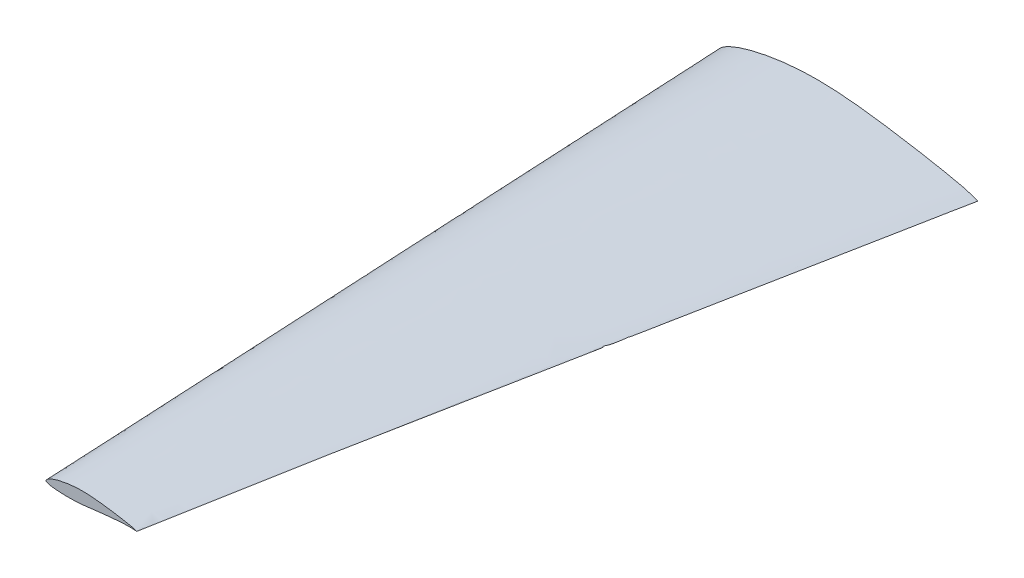
SolidWorks part; units mm, degrees
ref_plane "Front Plane" through (0, 0, 0) normal (0, 0, 1) x (1, 0, 0)
ref_plane "Top Plane" through (0, 0, 0) normal (0, 1, 0) x (1, 0, 0)
ref_plane "Right Plane" through (0, 0, 0) normal (1, 0, 0) x (0, 0, -1)
curve "Curve1"
  spline degree 3 poles (0.9921, 0.0008, 0) (1.0019, -0.0008, 0) (0.9929, 0.0016, 0) (0.9861, 0.0043, 0) (0.9706, 0.0096, 0) (0.9519, 0.0152, 0) (0.9278, 0.021, 0) (0.8992, 0.0273, 0) (0.8662, 0.0341, 0) (0.8293, 0.0413, 0) (0.789, 0.0488, 0) (0.746, 0.0564, 0) (0.7007, 0.0641, 0) (0.6538, 0.0714, 0) (0.6058, 0.0784, 0) (0.5573, 0.0846, 0) (0.5088, 0.0898, 0) (0.4609, 0.0938, 0) (0.4138, 0.0961, 0) (0.3679, 0.0966, 0) (0.3232, 0.0952, 0) (0.2801, 0.092, 0) (0.2388, 0.0874, 0) (0.1997, 0.0815, 0) (0.1631, 0.0746, 0) (0.1296, 0.0669, 0) (0.0993, 0.0585, 0) (0.0726, 0.0496, 0) (0.0499, 0.0404, 0) (0.0312, 0.031, 0) (0.0168, 0.0217, 0) (0.0085, 0.0145, 0) (0.0039, 0.009, 0) (0.0018, 0.0058, 0) (0.0004, 0.0024, 0) (0, 0.0003, 0) (0, -0.0012, 0) (0.0006, -0.0026, 0) (0.002, -0.0043, 0) (0.0049, -0.007, 0) (0.0107, -0.0108, 0) (0.0215, -0.0156, 0) (0.0378, -0.0206, 0) (0.0598, -0.0253, 0) (0.0864, -0.0294, 0) (0.1174, -0.033, 0) (0.1523, -0.036, 0) (0.1908, -0.0383, 0) (0.2323, -0.0397, 0) (0.2764, -0.0402, 0) (0.3228, -0.0395, 0) (0.3711, -0.0373, 0) (0.4212, -0.0335, 0) (0.4729, -0.0284, 0) (0.526, -0.0227, 0) (0.5798, -0.0169, 0) (0.6336, -0.0114, 0) (0.6866, -0.0064, 0) (0.7378, -0.0023, 0) (0.7866, 0.0009, 0) (0.832, 0.0031, 0) (0.8733, 0.0042, 0) (0.9096, 0.0045, 0) (0.9406, 0.0038, 0) (0.9645, 0.0029, 0) (0.984, 0.0013, 0) (0.9921, 0.0008, 0) (1.0019, -0.0008, 0) (0.9929, 0.0016, 0) knots -0.016161 -0.007282 -0.001839 0 0.00178 0.006777 0.014308 0.024046 0.036116 0.050547 0.06713 0.085624 0.105767 0.127282 0.149864 0.17323 0.197069 0.221103 0.245052 0.268663 0.291773 0.314299 0.336178 0.357377 0.377792 0.397225 0.415489 0.432417 0.447849 0.461651 0.473687 0.483898 0.492263 0.498797 0.499955 0.502811 0.504371 0.50536 0.505925 0.506503 0.507535 0.509205 0.512345 0.517665 0.526422 0.537425 0.550643 0.565966 0.583206 0.602155 0.622587 0.644255 0.666998 0.690703 0.715307 0.740824 0.767084 0.793717 0.820331 0.846519 0.871863 0.895937 0.918335 0.938667 0.956573 0.971715 0.983839 0.992718 0.998161 1 1.00178 1.006777 1.014308 periodic
sketch "Sketch1" plane through (0, 0, 0) normal (0, 0, 1) x (1, 0, 0)
  line L0 (1122.2059, -30.8288) -> (-1162.7941, -35.0845) construction
  spline S1 degree 3 poles (1104.1363, -28.0222) (1126.6295, -31.7875) (1105.8826, -26.3024) (1090.4575, -20.1288) (1054.9513, -7.9956) (1012.296, 4.6638) (957.0478, 17.8508) (891.7164, 32.0367) (816.2153, 47.3864) (731.9108, 63.6705) (639.9041, 80.612) (541.5101, 97.9168) (438.0076, 115.0958) (330.7593, 131.7488) (221.0675, 147.3336) (110.2357, 161.251) (-0.493, 172.9975) (-110.0556, 181.8587) (-217.6516, 186.9061) (-322.6724, 187.859) (-424.6755, 184.4831) (-523.1626, 176.9995) (-617.5035, 166.1709) (-706.8843, 152.6667) (-790.3524, 136.737) (-867.0563, 118.889) (-936.2082, 99.5088) (-997.0691, 79.0242) (-1049.0447, 57.9028) (-1091.6336, 36.4479) (-1124.4686, 15.1943) (-1143.3869, -1.4067) (-1153.8659, -14.0298) (-1158.6984, -21.3016) (-1161.9612, -29.0988) (-1162.8988, -33.8887) (-1162.7223, -37.2464) (-1161.3764, -40.4052) (-1158.2301, -44.4654) (-1151.5185, -50.6376) (-1138.2079, -59.2164) (-1113.635, -70.0567) (-1076.2399, -81.3981) (-1026.0446, -92.1031) (-965.2298, -101.4019) (-894.4776, -109.4657) (-814.6314, -116.0953) (-726.7099, -121.1028) (-631.8133, -124.2931) (-530.9633, -125.2112) (-425.0342, -123.2363) (-314.6436, -117.9744) (-200.1569, -109.1265) (-81.9663, -97.1903) (39.2548, -83.9633) (162.1641, -70.4688) (285.0306, -57.6215) (406.0083, -46.0046) (523.1884, -36.2734) (634.6311, -28.7415) (738.3789, -23.5277) (832.7109, -20.7776) (915.5317, -20.0924) (986.36, -21.3847) (1040.9806, -23.338) (1085.6437, -26.9173) (1104.1363, -28.0222) (1126.6295, -31.7875) (1105.8826, -26.3024) knots -0.016161 -0.007282 -0.001839 0 0.00178 0.006777 0.014308 0.024046 0.036116 0.050547 0.06713 0.085624 0.105767 0.127282 0.149864 0.17323 0.197069 0.221103 0.245052 0.268663 0.291773 0.314299 0.336178 0.357377 0.377792 0.397225 0.415489 0.432417 0.447849 0.461651 0.473687 0.483898 0.492263 0.498797 0.499955 0.502811 0.504371 0.50536 0.505925 0.506503 0.507535 0.509205 0.512345 0.517665 0.526422 0.537425 0.550643 0.565966 0.583206 0.602155 0.622587 0.644255 0.666998 0.690703 0.715307 0.740824 0.767084 0.793717 0.820331 0.846519 0.871863 0.895937 0.918335 0.938667 0.956573 0.971715 0.983839 0.992718 0.998161 1 1.00178 1.006777 1.014308 only from (1122.2059, -30.8288) to (1122.2059, -30.8288)
  dimension "D1" = 2285
ref_plane "Plane1" through (0, 0, 6200) normal (0, 0, 1) x (1, 0, 0)
ref_plane "Plane3" through (0, -35.0845, 0) normal (0, 1, 0) x (1, 0, 0)
sketch "Sketch4" plane through (0, -35.0845, 0) normal (0, 1, 0) x (1, 0, 0)
  line L1 (1122.2059, 0) -> (-1162.7941, 0) construction
  line L2 (-172.1886, -6200) -> (172.1886, -6200) construction
  line L4 (-1162.7941, 0) -> (-862.7941, -6200)
sketch "Sketch5" plane through (0, 0, 6200) normal (0, 0, 1) x (1, 0, 0)
  line L0 (-62.749, -35.2354) -> (-862.7688, -35.3009) construction
  spline S1 degree 3 poles (-69.0897, -34.3504) (-61.22, -35.5469) (-68.4893, -33.741) (-73.9048, -31.6671) (-86.3598, -27.6181) (-101.3126, -23.4229) (-120.663, -19.1093) (-143.5377, -14.4998) (-169.9677, -9.5373) (-199.4749, -4.2947) (-231.6736, 1.1372) (-266.1033, 6.6624) (-302.3153, 12.1171) (-339.8318, 17.3686) (-378.1955, 22.2345) (-416.9483, 26.5125) (-455.6538, 30.0335) (-493.9373, 32.5536) (-531.5145, 33.7529) (-568.1715, 33.5367) (-603.7528, 31.8256) (-638.0855, 28.6992) (-670.9538, 24.4271) (-702.0769, 19.2472) (-731.124, 13.2516) (-757.8002, 6.6219) (-781.8329, -0.5031) (-802.9662, -7.9701) (-820.9952, -15.6131) (-835.7466, -23.3233) (-847.0949, -30.9123) (-853.6106, -36.8049) (-857.2018, -41.2651) (-858.8503, -43.8282) (-859.9483, -46.5664) (-860.2505, -48.243) (-860.1714, -49.4139) (-859.6851, -50.5093) (-858.5659, -51.9099) (-856.1913, -54.0289) (-851.5011, -56.9533) (-842.8685, -60.6082) (-829.7584, -64.3709) (-812.1844, -67.8447) (-790.9116, -70.7722) (-766.1771, -73.2167) (-738.2762, -75.1133) (-707.5656, -76.4015) (-674.4302, -77.0191) (-639.2289, -76.8125) (-602.2702, -75.5698) (-563.7715, -73.1566) (-523.8621, -69.4706) (-482.6761, -64.6873) (-440.4393, -59.4377) (-397.6147, -54.086) (-354.8016, -48.9603) (-312.6413, -44.2739) (-271.7964, -40.2655) (-232.9425, -37.0546) (-196.7619, -34.6929) (-163.8546, -33.2402) (-134.9538, -32.5684) (-110.2281, -32.6493) (-91.1554, -33.0456) (-75.5494, -34.0614) (-69.0897, -34.3504) (-61.22, -35.5469) (-68.4893, -33.741) knots -0.016161 -0.007282 -0.001839 0 0.00178 0.006777 0.014308 0.024046 0.036116 0.050547 0.06713 0.085624 0.105767 0.127282 0.149864 0.17323 0.197069 0.221103 0.245052 0.268663 0.291773 0.314299 0.336178 0.357377 0.377792 0.397225 0.415489 0.432417 0.447849 0.461651 0.473687 0.483898 0.492263 0.498797 0.499955 0.502811 0.504371 0.50536 0.505925 0.506503 0.507535 0.509205 0.512345 0.517665 0.526422 0.537425 0.550643 0.565966 0.583206 0.602155 0.622587 0.644255 0.666998 0.690703 0.715307 0.740824 0.767084 0.793717 0.820331 0.846519 0.871863 0.895937 0.918335 0.938667 0.956573 0.971715 0.983839 0.992718 0.998161 1 1.00178 1.006777 1.014308 only from (-62.7688, -35.2354) to (-62.7688, -35.2354)
  point P3 (-862.7688, -35.3009)
  point P4 (0, 0)
  dimension "D1" = 800
sketch "Sketch6" plane through (0, 0, 6200) normal (0, 0, 1) x (1, 0, 0)
  line L0 (-862.7688, -35.3009) -> (-860.1517, -49.246)
  spline S0 degree 3 poles (-69.0897, -34.3504) (-61.22, -35.5469) (-68.4893, -33.741) (-73.9048, -31.6671) (-86.3598, -27.6181) (-101.3126, -23.4229) (-120.663, -19.1093) (-143.5377, -14.4998) (-169.9677, -9.5373) (-199.4749, -4.2947) (-231.6736, 1.1372) (-266.1033, 6.6624) (-302.3153, 12.1171) (-339.8318, 17.3686) (-378.1955, 22.2345) (-416.9483, 26.5125) (-455.6538, 30.0335) (-493.9373, 32.5536) (-531.5145, 33.7529) (-568.1715, 33.5367) (-603.7528, 31.8256) (-638.0855, 28.6992) (-670.9538, 24.4271) (-702.0769, 19.2472) (-731.124, 13.2516) (-757.8002, 6.6219) (-781.8329, -0.5031) (-802.9662, -7.9701) (-820.9952, -15.6131) (-835.7466, -23.3233) (-847.0949, -30.9123) (-853.6106, -36.8049) (-857.2018, -41.2651) (-858.8503, -43.8282) (-859.9483, -46.5664) (-860.2505, -48.243) (-860.1714, -49.4139) (-859.6851, -50.5093) (-858.5659, -51.9099) (-856.1913, -54.0289) (-851.5011, -56.9533) (-842.8685, -60.6082) (-829.7584, -64.3709) (-812.1844, -67.8447) (-790.9116, -70.7722) (-766.1771, -73.2167) (-738.2762, -75.1133) (-707.5656, -76.4015) (-674.4302, -77.0191) (-639.2289, -76.8125) (-602.2702, -75.5698) (-563.7715, -73.1566) (-523.8621, -69.4706) (-482.6761, -64.6873) (-440.4393, -59.4377) (-397.6147, -54.086) (-354.8016, -48.9603) (-312.6413, -44.2739) (-271.7964, -40.2655) (-232.9425, -37.0546) (-196.7619, -34.6929) (-163.8546, -33.2402) (-134.9538, -32.5684) (-110.2281, -32.6493) (-91.1554, -33.0456) (-75.5494, -34.0614) (-69.0897, -34.3504) (-61.22, -35.5469) (-68.4893, -33.741) knots -0.016161 -0.007282 -0.001839 0 0.00178 0.006777 0.014308 0.024046 0.036116 0.050547 0.06713 0.085624 0.105767 0.127282 0.149864 0.17323 0.197069 0.221103 0.245052 0.268663 0.291773 0.314299 0.336178 0.357377 0.377792 0.397225 0.415489 0.432417 0.447849 0.461651 0.473687 0.483898 0.492263 0.498797 0.499955 0.502811 0.504371 0.50536 0.505925 0.506503 0.507535 0.509205 0.512345 0.517665 0.526422 0.537425 0.550643 0.565966 0.583206 0.602155 0.622587 0.644255 0.666998 0.690703 0.715307 0.740824 0.767084 0.793717 0.820331 0.846519 0.871863 0.895937 0.918335 0.938667 0.956573 0.971715 0.983839 0.992718 0.998161 1 1.00178 1.006777 1.014308 only from (-62.7688, -35.2354) to (-62.7688, -35.2354) construction
ref_axis "Axis2" through (-860.1517, -49.246, 6200) along (-0.0488, 0.0023, -0.9988)
loft "Loft5" add profiles "Sketch1", "Sketch5" connector at (-829.2128, 127.5517, 0) connector at (-729.5824, 13.4038, 6200)
